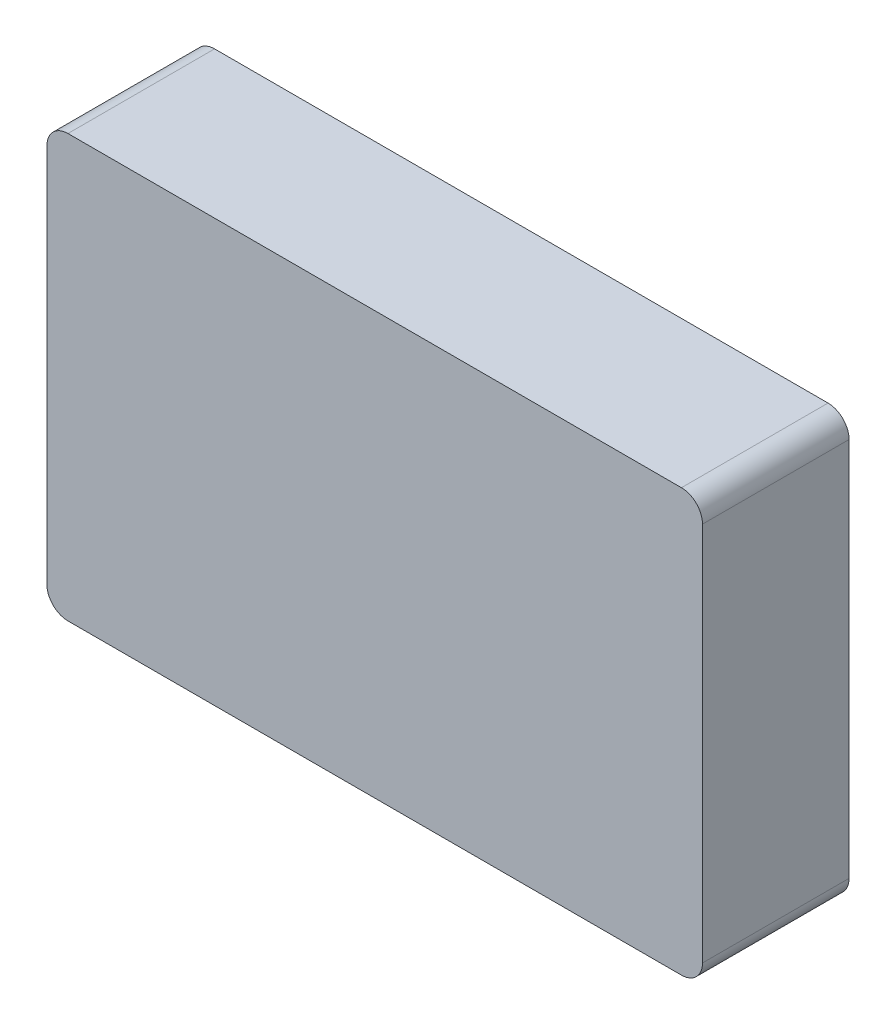
SolidWorks part; units mm, degrees
ref_plane "Front" through (0, 0, 0) normal (0, 0, 1) x (1, 0, 0)
ref_plane "Top" through (0, 0, 0) normal (0, 1, 0) x (1, 0, 0)
ref_plane "Right" through (0, 0, 0) normal (1, 0, 0) x (0, 0, -1)
sketch "Sketch1" plane through (0, 0, 0) normal (0, 0, 1) x (1, 0, 0)
  line L1 (-40.8, -28.075) -> (40.8, -28.075)
  line L2 (-43.6, -25.275) -> (-43.6, 25.275)
  line L3 (-40.8, 28.075) -> (40.8, 28.075)
  line L4 (43.6, -25.275) -> (43.6, 25.275)
  line L5 (-43.6, -28.075) -> (43.6, 28.075) construction
  line L6 (-43.6, 28.075) -> (43.6, -28.075) construction
  arc A0 (-40.8, -28.075) -> (-43.6, -25.275) centre (-40.8, -25.275) cw
  arc A1 (40.8, -28.075) -> (43.6, -25.275) centre (40.8, -25.275) ccw
  arc A2 (40.8, 28.075) -> (43.6, 25.275) centre (40.8, 25.275) cw
  arc A3 (-43.6, 25.275) -> (-40.8, 28.075) centre (-40.8, 25.275) cw
  point P0 (0, 0)
  dimension "D3" = 2.8
  dimension "D1" = 87.2
  dimension "D2" = 56.15
extrude "Boss-Extrude1" add sketch "Sketch1" along normal blind 19.5
